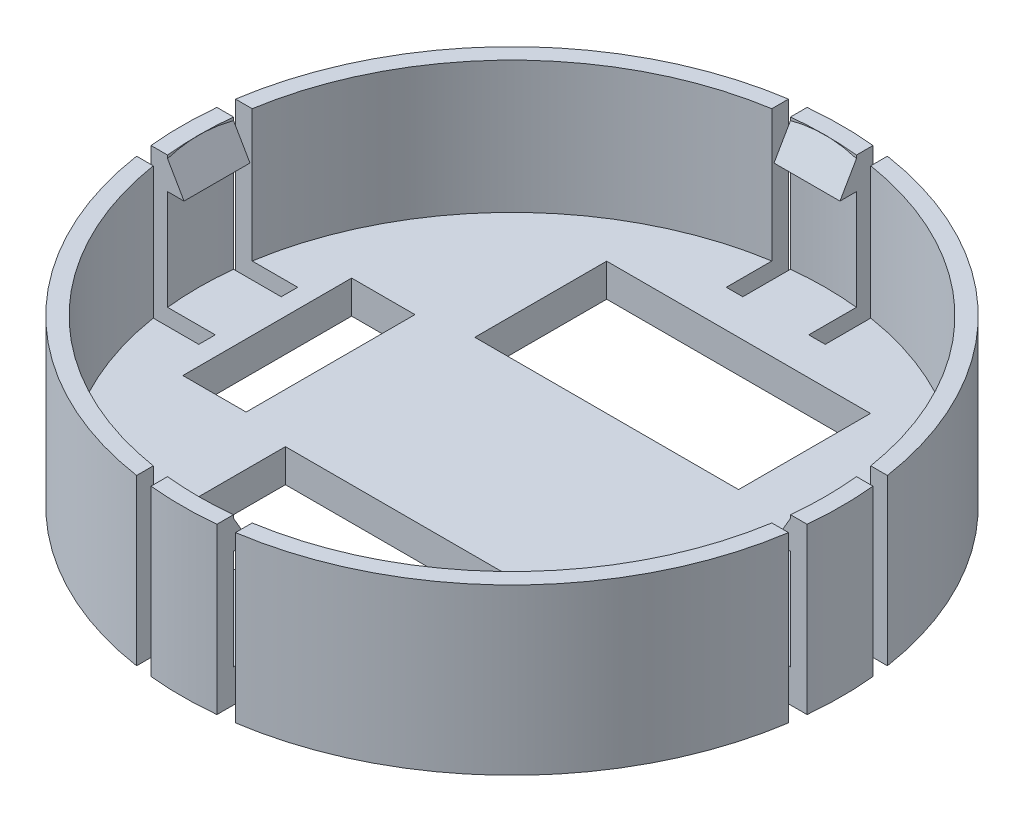
SolidWorks part; units mm, degrees
ref_plane "Front Plane" through (0, 0, 0) normal (0, 0, 1) x (1, 0, 0)
ref_plane "Top Plane" through (0, 0, 0) normal (0, 1, 0) x (1, 0, 0)
ref_plane "Right Plane" through (0, 0, 0) normal (1, 0, 0) x (0, 0, -1)
sketch "Sketch1" plane through (0, 0, 0) normal (0, 1, 0) x (1, 0, 0)
  circle A0 centre (0, 0) radius 15.875
  circle A1 centre (0, 0) radius 15.0813
  dimension "D1" = 30.1625
  dimension "D2" = 0.7937
extrude "Boss-Extrude1" add sketch "Sketch1" along normal blind 1.5875 contours A0
extrude "Boss-Extrude2" add sketch "Sketch1<3>" along normal blind 6.35 from surface starting at face at (0, 1.5875, 15.875)
sketch "Sketch1<3>" plane through (0, 0, 0) normal (0, 1, 0) x (1, 0, 0) same geometry as "Sketch1"
sketch "Sketch3" plane through (0, 7.9375, 0) normal (0, 1, 0) x (1, 0, 0)
  line L0 (-1.5875, 15.875) -> (1.5875, 15.875) construction
  line L1 (2.3812, 15.875) -> (1.5875, 15.875)
  line L2 (2.3812, 15.875) -> (2.3812, 12.7)
  line L3 (2.3812, 12.7) -> (1.5875, 12.7)
  line L4 (1.5875, 15.875) -> (1.5875, 12.7)
  line L5 (-1.5875, 15.875) -> (-2.3812, 15.875)
  line L6 (-1.5875, 15.875) -> (-1.5875, 12.7)
  line L7 (-1.5875, 12.7) -> (-2.3812, 12.7)
  line L8 (-2.3812, 15.875) -> (-2.3812, 12.7)
  circle A0 centre (0, 0) radius 15.875 construction
  point P8 (0, 0)
  point P9 (0, 0)
  point P11 (0, 15.875)
  point P14 (0, 0)
  point P17 (0, 0)
  dimension "D1" = 3.175
  dimension "D2" = 0.7937
  dimension "D3" = 3.175
extrude "Cut-Extrude1" cut sketch "Sketch3" against normal up to surface (7.9375 mm away) up to face at (0, 0, 15.875)
sketch "Sketch4" plane through (0, 0, 0) normal (-1, 0, 0) x (0, 0, 1)
  line L0 (-15.7954, 7.9375) -> (-15.7954, 6.4135)
  line L1 (-15.7954, 0) -> (-15.7954, 7.9375) construction
  line L2 (-15.7954, 6.4135) -> (-14.2037, 6.4135)
  line L3 (-14.2037, 6.4135) -> (-15.0836, 7.9375)
  line L4 (-15.7954, 7.9375) -> (-15.0836, 7.9375)
  line L5 (-14.9975, 7.9375) -> (-15.7954, 7.9375) construction
  line L6 (-14.9975, 7.9375) -> (-15.0813, 7.9375) construction
  line L7 (-14.9975, 7.9375) -> (-15.0813, 7.9375) construction
  line L9 (-14.9975, 1.5875) -> (-14.9975, 7.9375) construction
  line L10 (-12.7, 1.5875) -> (-14.9975, 1.5875) construction
  point P10 (0, 0)
  point P13 (0, 0)
  dimension "D1" = 30
  dimension "D2" = 4.826
  dimension "D3" = 0.7937
extrude "Boss-Extrude3" add sketch "Sketch4" against normal mid plane 3.175
pattern_circular "CirPattern2" count 4 over 360 about axis through (0, 1.5875, 0) along (0, -1, 0) of "Cut-Extrude1", "Boss-Extrude3"
sketch "Sketch5" plane through (0, 1.5875, 0) normal (0, 1, 0) x (1, 0, 0)
  line L0 (-6.35, 4.5593) -> (-6.35, -4.5593) construction
  line L1 (6.35, 10.9093) -> (-6.35, 10.9093)
  line L2 (6.35, 10.9093) -> (6.35, 4.5593)
  line L3 (6.35, 4.5593) -> (-6.35, 4.5593)
  line L4 (-6.35, 10.9093) -> (-6.35, 4.5593)
  line L5 (6.35, -4.5593) -> (-6.35, -4.5593)
  line L6 (6.35, -4.5593) -> (6.35, -10.9093)
  line L7 (6.35, -10.9093) -> (-6.35, -10.9093)
  line L8 (-6.35, -4.5593) -> (-6.35, -10.9093)
  line L10 (-8.7376, 4.064) -> (-11.7856, 4.064)
  line L11 (-8.7376, 4.064) -> (-8.7376, -4.064)
  line L12 (-8.7376, -4.064) -> (-11.7856, -4.064)
  line L13 (-11.7856, 4.064) -> (-11.7856, -4.064)
  point P8 (0, 4.5593)
  point P9 (6.35, 7.7343)
  point P11 (-6.35, 0)
  point P12 (6.35, -7.7343)
  point P17 (-8.7376, 0)
  point P18 (-10.2616, 4.064)
  dimension "D1" = 6.35
  dimension "D2" = 12.7
  dimension "D3" = 15.4686
  dimension "D4" = 8.128
  dimension "D5" = 3.048
  dimension "D6" = 10.2616
extrude "Cut-Extrude2" cut sketch "Sketch5" against normal through all
